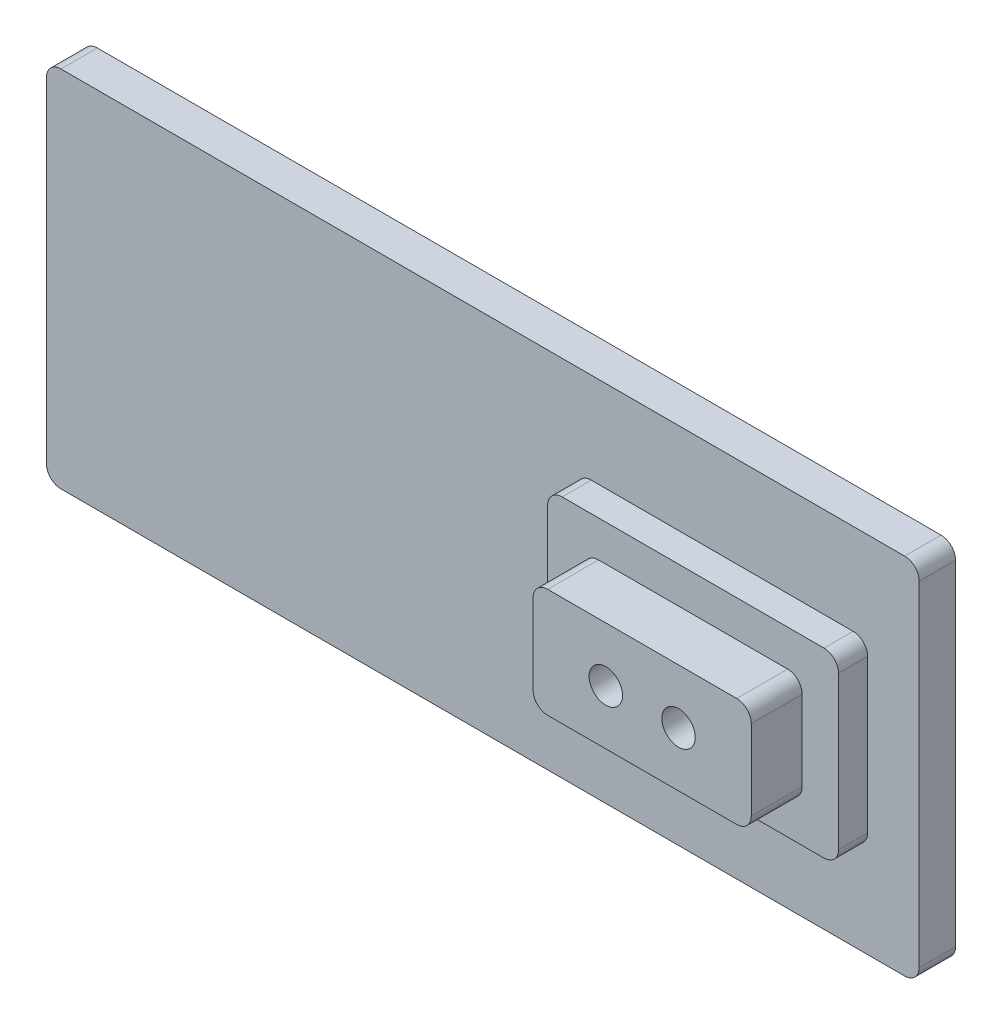
SolidWorks part; units mm, degrees
material "ABS"
ref_plane "Alzado" through (0, 0, 0) normal (0, 0, 1) x (1, 0, 0)
ref_plane "Planta" through (0, 0, 0) normal (0, 1, 0) x (1, 0, 0)
ref_plane "Vista lateral" through (0, 0, 0) normal (1, 0, 0) x (0, 0, -1)
sketch "Croquis1" plane through (0, 0, 0) normal (0, 0, 1) x (1, 0, 0)
  line L0 (-5, 0) -> (5, 0) construction
  line L5 (-15, -7.5) -> (15, -7.5)
  line L6 (-15, -7.5) -> (-15, 7.5)
  line L7 (-15, 7.5) -> (15, 7.5)
  line L8 (15, -7.5) -> (15, 7.5)
  line L9 (-15, -7.5) -> (15, 7.5) construction
  line L10 (-15, 7.5) -> (15, -7.5) construction
  circle A0 centre (5, 0) radius 2.3
  circle A1 centre (-5, 0) radius 2.3
  point P9 (0, 0)
  point P12 (0, 0)
  dimension "D2" = 4.6
  dimension "D1" = 5
  dimension "D3" = 30
  dimension "D4" = 15
extrude "Saliente-Extruir1" add sketch "Croquis1" along normal blind 16
sketch "Croquis2" plane through (0, 0, 0) normal (0, 0, -1) x (-1, 0, 0)
  line L0 (0, 0) -> (0, 25) construction
  line L1 (-27.0901, 25) -> (92.9099, 25)
  line L2 (-27.0901, 25) -> (-27.0901, -25)
  line L3 (0, 0) -> (-27.0901, 0) construction
  line L4 (-27.0901, -25) -> (92.9099, -25)
  line L5 (92.9099, -25) -> (92.9099, 25)
  circle A0 centre (-5, 0) radius 3.5
  circle A1 centre (5, 0) radius 3.5
  dimension "D1" = 120
  dimension "D2" = 50
extrude "Saliente-Extruir2" add sketch "Croquis2" against normal blind 5
sketch "Croquis3" plane through (0, 0, 5) normal (0, 0, 1) x (1, 0, 0)
  line L1 (-20, -12.5) -> (20, -12.5)
  line L2 (-20, -12.5) -> (-20, 12.5)
  line L3 (-20, 12.5) -> (20, 12.5)
  line L4 (20, -12.5) -> (20, 12.5)
  line L5 (-20, -12.5) -> (20, 12.5) construction
  line L6 (-20, 12.5) -> (20, -12.5) construction
  line L7 (-15, -7.5) -> (15, -7.5)
  line L8 (-15, -7.5) -> (-15, 7.5)
  line L9 (-15, 7.5) -> (15, 7.5)
  line L10 (15, -7.5) -> (15, 7.5)
  line L11 (-15, -7.5) -> (15, 7.5) construction
  line L12 (-15, 7.5) -> (15, -7.5) construction
  point P0 (0, 0)
  point P6 (0, 0)
  dimension "D1" = 40
  dimension "D2" = 25
extrude "Saliente-Extruir3" add sketch "Croquis3" along normal blind 4
sketch "Croquis4" plane through (0, 0, 0) normal (0, 0, -1) x (-1, 0, 0)
  line L0 (5, 7.5) -> (-5, 7.5)
  line L1 (5, -7.5) -> (-5, -7.5)
  arc A0 (-5, 7.5) -> (-5, -7.5) centre (-5, 0) ccw
  arc A1 (5, -7.5) -> (5, 7.5) centre (5, 0) ccw
  dimension "D1" = 15
extrude "Cortar-Extruir1" cut sketch "Croquis4" against normal blind 5
fillet "Redondeo1" radius 2 12 edges at (15, -7.5, 12.5) (15, 7.5, 12.5) (-15, 7.5, 12.5) (-15, -7.5, 12.5) (-20, -12.5, 7) (20, -12.5, 7) (20, 12.5, 7) (-20, 12.5, 7) (-92.9099, -25, 2.5) (-92.9099, 25, 2.5) (27.0901, -25, 2.5) (27.0901, 25, 2.5)
